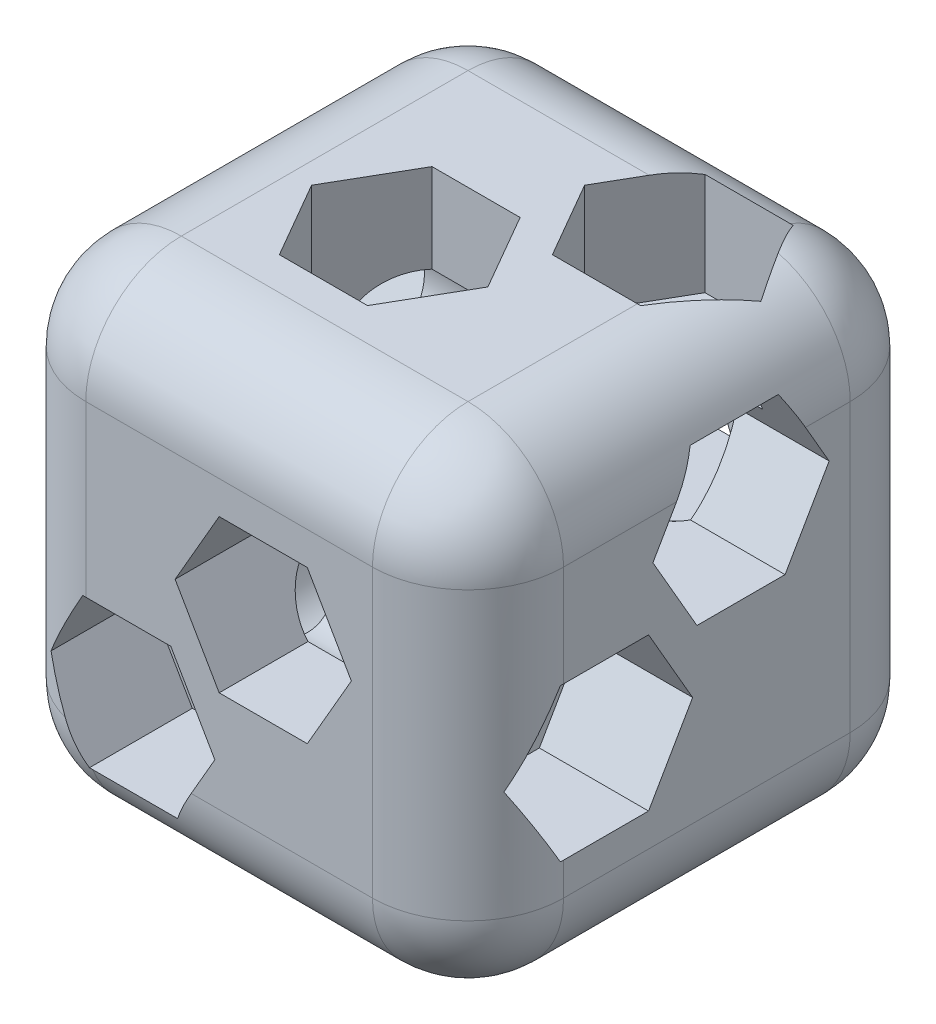
SolidWorks part; units mm, degrees
ref_plane "Front Plane" through (0, 0, 0) normal (0, 0, 1) x (1, 0, 0)
ref_plane "Top Plane" through (0, 0, 0) normal (0, 1, 0) x (1, 0, 0)
ref_plane "Right Plane" through (0, 0, 0) normal (1, 0, 0) x (0, 0, -1)
sketch "Sketch1" plane through (0, 0, 0) normal (0, 0, 1) x (1, 0, 0)
  line L1 (11.1125, -11.1125) -> (-11.1125, -11.1125)
  line L2 (11.1125, -11.1125) -> (11.1125, 11.1125)
  line L3 (11.1125, 11.1125) -> (-11.1125, 11.1125)
  line L4 (-11.1125, -11.1125) -> (-11.1125, 11.1125)
  line L5 (11.1125, -11.1125) -> (-11.1125, 11.1125) construction
  line L6 (11.1125, 11.1125) -> (-11.1125, -11.1125) construction
  point P0 (0, 0)
  dimension "D1" = 22.225
extrude "Boss-Extrude1" add sketch "Sketch1" along normal blind 22.225
sketch "Sketch5" plane through (0, 11.1125, 0) normal (0, 1, 0) x (1, 0, 0)
  line L0 (11.1125, -22.225) -> (-11.1125, -22.225) construction
  line L1 (-11.1125, -22.225) -> (-11.1125, 0) construction
  circle A0 centre (-1.5875, -12.7) radius 2.25
  circle A1 centre (4.7625, -6.35) radius 2.25
  dimension "D5" = 4.5
  dimension "D1" = 9.525
  dimension "D2" = 9.525
  dimension "D3" = 15.875
  dimension "D4" = 15.875
extrude "Cut-Extrude2" cut sketch "Sketch5" against normal blind 25.4
sketch "Sketch6" plane through (11.1125, 0, 0) normal (1, 0, 0) x (0, 0, -1)
  line L0 (-22.225, -11.1125) -> (-22.225, 11.1125) construction
  line L1 (-22.225, -11.1125) -> (0, -11.1125) construction
  circle A0 centre (-15.875, -1.5875) radius 2.25
  circle A1 centre (-9.525, 4.7625) radius 2.25
  dimension "D3" = 4.5
  dimension "D1" = 6.35
  dimension "D2" = 9.525
  dimension "D4" = 15.875
  dimension "D5" = 12.7
extrude "Cut-Extrude3" cut sketch "Sketch6" against normal blind 25.4
sketch "Sketch7" plane through (0, 0, 0) normal (0, 0, -1) x (-1, 0, 0)
  line L2 (11.1125, -11.1125) -> (-11.1125, -11.1125) construction
  line L3 (11.1125, 11.1125) -> (11.1125, -11.1125) construction
  circle A0 centre (-1.5875, 1.5875) radius 2.25
  circle A1 centre (4.7625, -4.7625) radius 2.25
  dimension "D5" = 4.5
  dimension "D1" = 6.35
  dimension "D2" = 6.35
  dimension "D3" = 12.7
  dimension "D4" = 12.7
extrude "Cut-Extrude4" cut sketch "Sketch7" against normal blind 25.4
fillet "Fillet2" radius 4.445 12 edges at (-11.1125, 0, 22.225) (0, -11.1125, 22.225) (11.1125, -11.1125, 11.1125) (0, -11.1125, 0) (-11.1125, -11.1125, 11.1125) (-11.1125, 0, 0) (11.1125, 0, 0) (11.1125, 0, 22.225) (0, 11.1125, 22.225) (-11.1125, 11.1125, 11.1125) (0, 11.1125, 0) (11.1125, 11.1125, 11.1125)
sketch "Sketch8" plane through (-11.1125, 0, 0) normal (-1, 0, 0) x (0, 0, 1)
  line L1 (5.4258, 4.7625) -> (7.4754, 1.2125)
  line L2 (7.4754, 1.2125) -> (11.5746, 1.2125)
  line L3 (11.5746, 1.2125) -> (13.6242, 4.7625)
  line L4 (13.6242, 4.7625) -> (11.5746, 8.3125)
  line L5 (11.5746, 8.3125) -> (7.4754, 8.3125)
  line L6 (7.4754, 8.3125) -> (5.4258, 4.7625)
  line L7 (13.8254, 1.9625) -> (11.7758, -1.5875)
  line L8 (11.7758, -1.5875) -> (13.8254, -5.1375)
  line L9 (13.8254, -5.1375) -> (17.9246, -5.1375)
  line L10 (17.9246, -5.1375) -> (19.9742, -1.5875)
  line L11 (19.9742, -1.5875) -> (17.9246, 1.9625)
  line L12 (17.9246, 1.9625) -> (13.8254, 1.9625)
  circle A0 centre (9.525, 4.7625) radius 3.55 construction
  circle A1 centre (15.875, -1.5875) radius 3.55 construction
  dimension "D1" = 7.1
extrude "Cut-Extrude5" cut sketch "Sketch8" against normal blind 5.25
sketch "Sketch9" plane through (0, -11.1125, 0) normal (0, -1, 0) x (1, 0, 0)
  line L1 (-3.6371, 16.25) -> (-5.6867, 12.7)
  line L2 (-5.6867, 12.7) -> (-3.6371, 9.15)
  line L3 (-3.6371, 9.15) -> (0.4621, 9.15)
  line L4 (0.4621, 9.15) -> (2.5117, 12.7)
  line L5 (2.5117, 12.7) -> (0.4621, 16.25)
  line L6 (0.4621, 16.25) -> (-3.6371, 16.25)
  line L7 (2.7129, 9.9) -> (0.6633, 6.35)
  line L8 (0.6633, 6.35) -> (2.7129, 2.8)
  line L9 (2.7129, 2.8) -> (6.8121, 2.8)
  line L10 (6.8121, 2.8) -> (8.8617, 6.35)
  line L11 (8.8617, 6.35) -> (6.8121, 9.9)
  line L12 (6.8121, 9.9) -> (2.7129, 9.9)
  circle A0 centre (-1.5875, 12.7) radius 3.55 construction
  circle A1 centre (4.7625, 6.35) radius 3.55 construction
  dimension "D1" = 7.1
extrude "Cut-Extrude6" cut sketch "Sketch9" against normal blind 5.1
sketch "Sketch10" plane through (0, 0, 22.225) normal (0, 0, -1) x (-1, 0, 0)
  line L1 (-3.6371, 5.1375) -> (-5.6867, 1.5875)
  line L2 (-5.6867, 1.5875) -> (-3.6371, -1.9625)
  line L3 (-3.6371, -1.9625) -> (0.4621, -1.9625)
  line L4 (0.4621, -1.9625) -> (2.5117, 1.5875)
  line L5 (2.5117, 1.5875) -> (0.4621, 5.1375)
  line L6 (0.4621, 5.1375) -> (-3.6371, 5.1375)
  line L7 (2.7129, -1.2125) -> (0.6633, -4.7625)
  line L8 (0.6633, -4.7625) -> (2.7129, -8.3125)
  line L9 (2.7129, -8.3125) -> (6.8121, -8.3125)
  line L10 (6.8121, -8.3125) -> (8.8617, -4.7625)
  line L11 (8.8617, -4.7625) -> (6.8121, -1.2125)
  line L12 (6.8121, -1.2125) -> (2.7129, -1.2125)
  circle A0 centre (-1.5875, 1.5875) radius 3.55 construction
  circle A1 centre (4.7625, -4.7625) radius 3.55 construction
  dimension "D1" = 7.1
extrude "Cut-Extrude7" cut sketch "Sketch10" along normal blind 5.1
sketch "Sketch11" plane through (11.1125, 0, 0) normal (1, 0, 0) x (0, 0, -1)
  line L0 (-7.4754, 8.3125) -> (-6.5257, 6.6675) construction
  line L1 (-7.4754, 8.3125) -> (-11.5746, 8.3125) construction
  line L2 (-12.5243, 6.6675) -> (-11.5746, 8.3125) construction
  line L3 (-17.78, 6.6675) -> (-17.78, 11.1125) construction
  line L4 (-17.78, 11.1125) -> (-4.445, 11.1125) construction
  line L5 (-4.445, 11.1125) -> (-4.445, 6.6675) construction
  line L6 (-11.7758, -1.5875) -> (-13.8254, 1.9625) construction
  line L7 (-13.8254, 1.9625) -> (-17.78, 1.9625) construction
  line L8 (-17.78, 1.9625) -> (-17.78, 6.6675) construction
  line L9 (-12.5243, 6.6675) -> (-13.6242, 4.7625) construction
  line L10 (-13.6242, 4.7625) -> (-11.5746, 1.2125) construction
  line L11 (-11.5746, 1.2125) -> (-7.4754, 1.2125) construction
  line L12 (-7.4754, 1.2125) -> (-5.4258, 4.7625) construction
  line L13 (-5.4258, 4.7625) -> (-6.5257, 6.6675) construction
  line L14 (-4.445, 6.6675) -> (-4.445, -6.6675) construction
  line L15 (-4.445, -6.6675) -> (-17.78, -6.6675) construction
  line L16 (-17.78, -6.6675) -> (-17.78, -5.1375) construction
  line L17 (-17.78, -5.1375) -> (-13.8254, -5.1375) construction
  line L18 (-13.8254, -5.1375) -> (-11.7758, -1.5875) construction
  line L19 (-19.9742, -1.5875) -> (-17.9246, 1.9625) construction
  line L20 (-17.9246, -5.1375) -> (-19.9742, -1.5875) construction
  line L21 (-7.4754, 8.3125) -> (-6.5257, 6.6675)
  line L22 (-7.4754, 8.3125) -> (-11.5746, 8.3125)
  line L23 (-12.5243, 6.6675) -> (-11.5746, 8.3125)
  line L24 (-17.78, 6.6675) -> (-17.78, 11.1125)
  line L25 (-17.78, 11.1125) -> (-4.445, 11.1125)
  line L26 (-4.445, 11.1125) -> (-4.445, 6.6675)
  line L27 (-11.7758, -1.5875) -> (-13.8254, 1.9625)
  line L28 (-13.8254, 1.9625) -> (-17.78, 1.9625)
  line L29 (-17.78, 1.9625) -> (-17.78, 6.6675)
  line L30 (-12.5243, 6.6675) -> (-13.6242, 4.7625)
  line L31 (-13.6242, 4.7625) -> (-11.5746, 1.2125)
  line L32 (-11.5746, 1.2125) -> (-7.4754, 1.2125)
  line L33 (-7.4754, 1.2125) -> (-5.4258, 4.7625)
  line L34 (-5.4258, 4.7625) -> (-6.5257, 6.6675)
  line L35 (-4.445, 6.6675) -> (-4.445, -6.6675)
  line L36 (-4.445, -6.6675) -> (-17.78, -6.6675)
  line L37 (-17.78, -6.6675) -> (-17.78, -5.1375)
  line L38 (-17.78, -5.1375) -> (-13.8254, -5.1375)
  line L39 (-13.8254, -5.1375) -> (-11.7758, -1.5875)
  line L40 (-19.9742, -1.5875) -> (-17.9246, 1.9625)
  line L41 (-17.9246, -5.1375) -> (-19.9742, -1.5875)
  line L42 (-17.9246, 1.9625) -> (-17.78, 1.9625)
  line L43 (-17.9246, -5.1375) -> (-17.78, -5.1375)
  point P23 (-17.7745, -5.1375)
  arc M1 (-17.78, -0.3902) -> (-17.78, -2.7848) centre (-15.875, -1.5875) cw
  line M2 (-17.78, -2.7848) -> (-17.78, -6.6675)
  line M5 (-4.445, 6.6675) -> (-8.3277, 6.6675)
  arc M6 (-8.3277, 6.6675) -> (-10.7223, 6.6675) centre (-9.525, 4.7625) cw
  line M7 (-10.7223, 6.6675) -> (-17.78, 6.6675)
  line M8 (-17.78, 6.6675) -> (-17.78, -0.3902)
extrude "Cut-Extrude8" cut sketch "Sketch11" against normal blind 5.08 contours L38 L39 L27 L28 M8 M1 M2 | L33 L34 L30 L31 L32 M5 M6 M7 | L23 L21 L22 M7 M6 M5 | L41 L43 L42 L40 M2 M1 M8 region at (11.1125, 5.6539, 9.525) region at (11.1125, 5.6658, 6.061) region at (11.1125, -1.5875, 16.7533) region at (11.1125, 1.8695, 15.8027)
sketch "Sketch12" plane through (0, 0, 0) normal (0, 0, -1) x (-1, 0, 0)
  line L0 (6.8121, -8.3125) -> (6.6675, -8.3125) construction
  line L1 (7.7618, -6.6675) -> (6.8121, -8.3125) construction
  line L2 (2.7129, -8.3125) -> (1.7632, -6.6675) construction
  line L3 (2.7129, -8.3125) -> (6.6675, -8.3125) construction
  line L4 (6.6675, -11.1125) -> (-6.6675, -11.1125) construction
  line L5 (-6.6675, -11.1125) -> (-6.6675, -6.6675) construction
  line L6 (6.8121, -1.2125) -> (8.8617, -4.7625) construction
  line L7 (6.6675, -1.2125) -> (6.8121, -1.2125) construction
  line L8 (6.6675, 6.6675) -> (11.1125, 6.6675) construction
  line L9 (11.1125, 6.6675) -> (11.1125, 1.9625) construction
  line L10 (11.1101, 1.9625) -> (11.1125, 1.9625) construction
  line L11 (11.1125, -5.1375) -> (11.1101, -5.1375) construction
  line L12 (11.1125, -5.1375) -> (11.1125, -6.6675) construction
  line L13 (8.8617, -4.7625) -> (7.7618, -6.6675) construction
  line L14 (6.6675, -1.2125) -> (2.7129, -1.2125) construction
  line L15 (2.7129, -1.2125) -> (0.6633, -4.7625) construction
  line L16 (0.6633, -4.7625) -> (1.7632, -6.6675) construction
  line L17 (-6.6675, -6.6675) -> (-6.6675, 6.6675) construction
  line L18 (-6.6675, 6.6675) -> (6.6675, 6.6675) construction
  line L19 (6.8121, -8.3125) -> (6.6675, -8.3125)
  line L20 (7.7618, -6.6675) -> (6.8121, -8.3125)
  line L21 (2.7129, -8.3125) -> (1.7632, -6.6675)
  line L22 (2.7129, -8.3125) -> (6.6675, -8.3125)
  line L23 (6.6675, -11.1125) -> (-6.6675, -11.1125)
  line L24 (-6.6675, -11.1125) -> (-6.6675, -6.6675)
  line L25 (6.8121, -1.2125) -> (8.8617, -4.7625)
  line L26 (6.6675, -1.2125) -> (6.8121, -1.2125)
  line L27 (6.6675, 6.6675) -> (11.1125, 6.6675)
  line L28 (11.1125, 6.6675) -> (11.1125, 1.9625)
  line L29 (11.1101, 1.9625) -> (11.1125, 1.9625)
  line L30 (11.1125, -5.1375) -> (11.1101, -5.1375)
  line L31 (11.1125, -5.1375) -> (11.1125, -6.6675)
  line L32 (8.8617, -4.7625) -> (7.7618, -6.6675)
  line L33 (6.6675, -1.2125) -> (2.7129, -1.2125)
  line L34 (2.7129, -1.2125) -> (0.6633, -4.7625)
  line L35 (0.6633, -4.7625) -> (1.7632, -6.6675)
  line L36 (-6.6675, -6.6675) -> (-6.6675, 6.6675)
  line L37 (-6.6675, 6.6675) -> (6.6675, 6.6675)
  line L38 (-5.6867, 1.5875) -> (-3.6371, -1.9625) construction
  line L39 (-3.6371, 5.1375) -> (-5.6867, 1.5875) construction
  line L40 (0.4621, 5.1375) -> (-3.6371, 5.1375) construction
  line L41 (2.5117, 1.5875) -> (0.4621, 5.1375) construction
  line L42 (-3.6371, -1.9625) -> (0.4621, -1.9625) construction
  line L43 (0.4621, -1.9625) -> (2.5117, 1.5875) construction
  line L44 (-5.6867, 1.5875) -> (-3.6371, -1.9625)
  line L45 (-3.6371, 5.1375) -> (-5.6867, 1.5875)
  line L46 (0.4621, 5.1375) -> (-3.6371, 5.1375)
  line L47 (2.5117, 1.5875) -> (0.4621, 5.1375)
  line L48 (-3.6371, -1.9625) -> (0.4621, -1.9625)
  line L49 (0.4621, -1.9625) -> (2.5117, 1.5875)
  arc A0 (6.6675, -11.1125) -> (11.1125, -6.6675) centre (6.6675, -6.6675) ccw construction
  arc A1 (6.6675, -11.1125) -> (11.1125, -6.6675) centre (6.6675, -6.6675) ccw
  ellipse E0 centre (6.6675, 2.2129) end of major axis (6.6675, 9.9119) minor radius 4.445 (10.5332, -1.5875) -> (11.1101, 1.9625) ccw construction
  ellipse E1 centre (6.6675, -5.3879) end of major axis (6.6675, 2.311) minor radius 4.445 (11.1101, -5.1375) -> (10.5332, -1.5875) ccw construction
  ellipse E2 centre (6.6675, 2.2129) end of major axis (6.6675, 9.9119) minor radius 4.445 (10.5332, -1.5875) -> (11.1101, 1.9625) ccw
  ellipse E3 centre (6.6675, -5.3879) end of major axis (6.6675, 2.311) minor radius 4.445 (11.1101, -5.1375) -> (10.5332, -1.5875) ccw
  circle M2 centre (-1.5875, 1.5875) radius 2.25
  line M4 (-6.6675, -6.6675) -> (3.5652, -6.6675)
  arc M5 (3.5652, -6.6675) -> (6.6675, -3.5652) centre (4.7625, -4.7625) cw
  line M6 (6.6675, -3.5652) -> (6.6675, 6.6675)
extrude "Cut-Extrude9" cut sketch "Sketch12" against normal blind 5.08 contours L48 L49 L47 L46 L45 L44 M2 | L34 L35 L33 M4 M5 M6 | L32 L25 L26 L21 L22 L19 L20 M6 M5 M4 region at (-5.3775, -5.3796, 0) region at (-1.2835, -5.6744, 0) region at (4.568, 3.3083, 0)
sketch "Sketch14" plane through (0, 11.1125, 0) normal (0, 1, 0) x (1, 0, 0)
  line L0 (-2.8917, -16.25) -> (-2.8917, -14.5335) construction
  line L1 (-2.8917, -10.8665) -> (-2.8917, -9.15) construction
  line L2 (-2.8917, -9.15) -> (0.4621, -9.15) construction
  line L3 (0.4621, -9.15) -> (2.5117, -12.7) construction
  line L4 (2.5117, -12.7) -> (0.4621, -16.25) construction
  line L5 (0.4621, -16.25) -> (-2.8917, -16.25) construction
  line L6 (6.8121, -9.9) -> (2.7129, -9.9) construction
  line L7 (2.7129, -9.9) -> (0.6633, -6.35) construction
  line L8 (0.6633, -6.35) -> (2.7129, -2.8) construction
  line L9 (2.7129, -2.8) -> (6.8121, -2.8) construction
  line L10 (6.8121, -2.8) -> (8.8617, -6.35) construction
  line L11 (8.8617, -6.35) -> (6.8121, -9.9) construction
  line L12 (-3.6371, -9.15) -> (0.4621, -9.15) construction
  line L13 (0.4621, -16.25) -> (-3.6371, -16.25) construction
  line L14 (-3.6371, -16.25) -> (-5.6867, -12.7) construction
  line L15 (-5.6867, -12.7) -> (-3.6371, -9.15) construction
  line L16 (-2.8917, -16.25) -> (-2.8917, -14.5335)
  line L17 (-2.8917, -10.8665) -> (-2.8917, -9.15)
  line L18 (-2.8917, -9.15) -> (0.4621, -9.15)
  line L19 (0.4621, -9.15) -> (2.5117, -12.7)
  line L20 (2.5117, -12.7) -> (0.4621, -16.25)
  line L21 (0.4621, -16.25) -> (-2.8917, -16.25)
  line L22 (6.8121, -9.9) -> (2.7129, -9.9)
  line L23 (2.7129, -9.9) -> (0.6633, -6.35)
  line L24 (0.6633, -6.35) -> (2.7129, -2.8)
  line L25 (2.7129, -2.8) -> (6.8121, -2.8)
  line L26 (6.8121, -2.8) -> (8.8617, -6.35)
  line L27 (8.8617, -6.35) -> (6.8121, -9.9)
  line L28 (-3.6371, -9.15) -> (0.4621, -9.15)
  line L29 (0.4621, -16.25) -> (-3.6371, -16.25)
  line L30 (-3.6371, -16.25) -> (-5.6867, -12.7)
  line L31 (-5.6867, -12.7) -> (-3.6371, -9.15)
  arc A0 (-2.8917, -14.5335) -> (-2.8917, -10.8665) centre (-1.5875, -12.7) ccw construction
  arc A1 (-2.8917, -14.5335) -> (-2.8917, -10.8665) centre (-1.5875, -12.7) ccw
  circle M1 centre (-1.5875, -12.7) radius 2.25
  arc M2 (6.6675, -7.5473) -> (3.5652, -4.445) centre (4.7625, -6.35) cw
  line M3 (3.5652, -4.445) -> (-6.6675, -4.445)
  line M6 (6.6675, -17.78) -> (6.6675, -7.5473)
extrude "Cut-Extrude10" cut sketch "Sketch14" against normal blind 5.08 contours L21 L20 L19 L18 L17 L16 M1 | L31 L30 L29 L16 L17 L28 M1 | L24 L23 L22 M6 M2 M3 | L27 L26 L25 L24 L22 M3 M2 M6 region at (-4.019, 11.1125, 12.7) region at (-2.8024, 11.1125, 15.3917) region at (5.3775, 11.1125, 5.7329) region at (4.6902, 11.1125, 9.8189)
